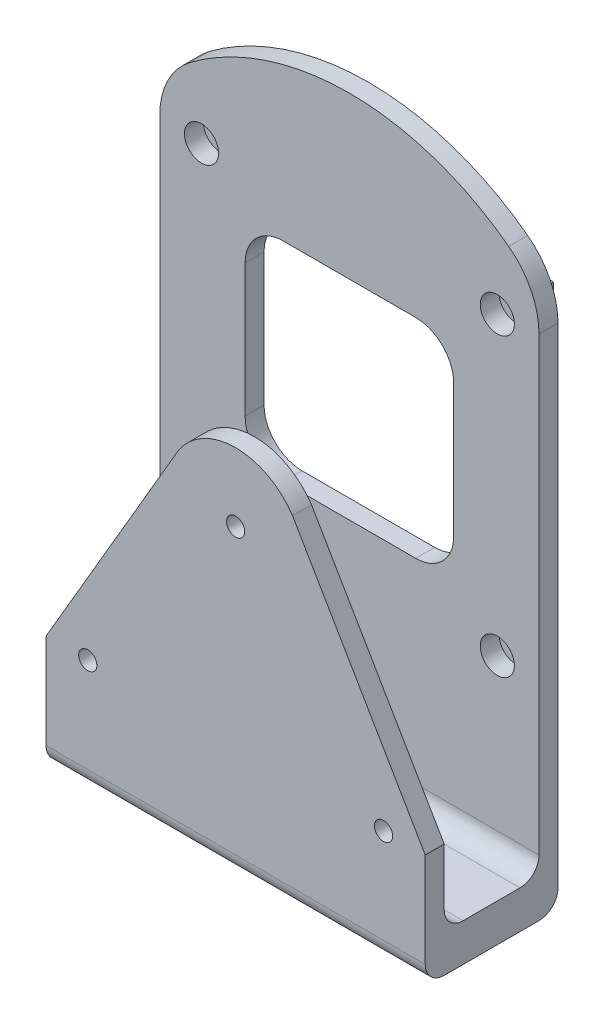
SolidWorks part; units mm, degrees
ref_plane "Спереди" through (0, 0, 0) normal (0, 0, 1) x (1, 0, 0)
ref_plane "Сверху" through (0, 0, 0) normal (0, 1, 0) x (1, 0, 0)
ref_plane "Справа" through (0, 0, 0) normal (1, 0, 0) x (0, 0, -1)
sketch "Эскиз1" plane through (0, 0, 0) normal (0, 0, 1) x (1, 0, 0)
  line L0 (50, 0) -> (-50, 0) construction
  line L1 (45, -46.9042) -> (45, 46.9042)
  line L2 (0, 0) -> (0, -65) construction
  line L3 (50, -48.9898) -> (50, 48.9898)
  line L4 (-50, -48.9898) -> (-50, 48.9898)
  line L5 (-45, -46.9042) -> (-45, 46.9042)
  line L6 (17.5, -27.5) -> (-17.5, -27.5)
  line L7 (27.5, -17.5) -> (27.5, 17.5)
  line L8 (17.5, 27.5) -> (-17.5, 27.5)
  line L9 (-27.5, -17.5) -> (-27.5, 17.5)
  line L10 (27.5, -27.5) -> (-27.5, 27.5) construction
  line L11 (27.5, 27.5) -> (-27.5, -27.5) construction
  line L12 (-33, -44.925) -> (-45, -44.925)
  line L13 (-33, -44.925) -> (-33, -33.075)
  line L14 (-33, -33.075) -> (-45, -33.075)
  line L15 (-45, -44.925) -> (-45, -33.075)
  line L16 (-0.1, 27.5) -> (0.1, 27.5)
  line L17 (-33, -44.925) -> (-45, -33.075) construction
  line L18 (-33, -33.075) -> (-45, -44.925) construction
  line L19 (33, -44.925) -> (45, -44.925)
  line L20 (33, -44.925) -> (33, -33.075)
  line L21 (33, -33.075) -> (45, -33.075)
  line L22 (-33, 33.075) -> (-45, 33.075)
  line L23 (-27.5, 0.1) -> (-27.5, -0.1)
  line L24 (-0.1, -27.5) -> (0.1, -27.5)
  line L25 (27.5, 0.1) -> (27.5, -0.1)
  line L26 (-33, 44.925) -> (-33, 33.075)
  line L27 (-33, 44.925) -> (-45, 44.925)
  line L28 (33, 44.925) -> (45, 44.925)
  line L29 (33, 44.925) -> (33, 33.075)
  line L30 (33, 33.075) -> (45, 33.075)
  arc A0 (-45, -46.9042) -> (45, -46.9042) centre (0, 0) ccw
  arc A1 (50, 48.9898) -> (-50, 48.9898) centre (0, 0) ccw
  arc A2 (45, 46.9042) -> (-45, 46.9042) centre (0, 0) ccw
  circle A3 centre (0, 0) radius 65 construction
  circle A4 centre (0, 0) radius 70 construction
  arc A5 (-50, -48.9898) -> (50, -48.9898) centre (0, 0) ccw
  circle A6 centre (-39, -39) radius 2.5
  circle A7 centre (39, -39) radius 4.5
  circle A8 centre (39, -39) radius 2.5
  circle A9 centre (-39, -39) radius 4.5
  circle A10 centre (39, 39) radius 2.5
  circle A11 centre (-39, 39) radius 4.5
  circle A12 centre (-39, 39) radius 2.5
  circle A13 centre (39, 39) radius 4.5
  arc A14 (17.5, -27.5) -> (27.5, -17.5) centre (17.5, -17.5) ccw
  arc A15 (-17.5, -27.5) -> (-27.5, -17.5) centre (-17.5, -17.5) cw
  arc A16 (-17.5, 27.5) -> (-27.5, 17.5) centre (-17.5, 17.5) ccw
  arc A17 (27.5, 17.5) -> (17.5, 27.5) centre (17.5, 17.5) ccw
  point P4 (66.9413, 20.466)
  point P14 (65, 0)
  dimension "D2" = 9
  dimension "D6" = 5
  dimension "D7" = 9
  dimension "D11" = 10
  dimension "D8" = 9
  dimension "D9" = 9
  dimension "D12" = 78
  dimension "D3" = 5
  dimension "D5" = 78
  dimension "D10" = 100
  dimension "D13" = 11.85
  dimension "D1" = 5
extrude "Extrude" add sketch "Эскиз1" along normal blind 5 contours L4 A5 L3 A1 A2 L1 A0 L5 | L1 A2 L5 A0 A8 A6 A10 A12 | L21 L20 L19 L1 A7 | L13 L14 L5 L12 A9 | L26 L27 L5 L22 A11 | L29 L30 L1 L28 A13 region at (0, -63.4189, 0) region at (39, -44.7564, 0) region at (-44.8314, -39, 0) region at (39, 33.2436, 0) region at (-44.8314, 39, 0) region at (0, -68.2795, 0)
fillet "Fillet1" radius 20 4 edges at (50, -48.9898, 2.5) (-50, -48.9898, 2.5) (-50, 48.9898, 2.5) (50, 48.9898, 2.5)
extrude "Boss-Extrude1" add sketch "Эскиз1<5>" against normal blind 3.85 contours L21 L20 L19 L1 A7 | L13 L14 L5 L12 A9 | L26 L27 L5 L22 A11 | L29 L30 L1 L28 A13 | A13 A10 | A11 A12 | A9 A6 | A7 A8 region at (39, -44.7564, 0) region at (-44.8314, -39, 0) region at (39, 33.2436, 0) region at (-44.8314, 39, 0) region at (34.6273, -39, 0) region at (-43.3727, -39, 0) region at (-43.3727, 39, 0) region at (34.6273, 39, 0)
sketch "Эскиз1<5>" plane through (0, 0, 0) normal (0, 0, 1) x (1, 0, 0) same geometry as "Эскиз1"
sketch "Sketch1" plane through (0, 0, 0) normal (0, 0, 1) x (1, 0, 0)
  line L0 (-50, -40) -> (-50, -84)
  line L1 (-50, -84) -> (50, -84)
  line L2 (50, -84) -> (50, -40)
  line L3 (-50, -84) -> (-50, -94)
  line L4 (-50, -94) -> (50, -94)
  line L5 (50, -94) -> (50, -84)
  circle A0 centre (-39, -39) radius 2.5 construction
  arc A1 (50, -40) -> (-50, -40) centre (0, 10) cw
  dimension "D1" = 45
  dimension "D2" = 10
extrude "Boss-Extrude3" add sketch "Sketch1" along normal blind 5 contours L2 A1 L0 L1 region at (0, -68.5287, 0)
extrude "Boss-Extrude4" add sketch "Sketch1<3>" along normal blind 30 contours L4 L5 L1 L3 region at (0, -89, 0)
sketch "Sketch1<3>" plane through (0, 0, 0) normal (0, 0, 1) x (1, 0, 0) same geometry as "Sketch1"
sketch "Sketch2" plane through (0, 0, 30) normal (0, 0, 1) x (1, 0, 0)
  line L1 (0, 0) -> (0, -84) construction
  line L2 (-50, -84) -> (50, -84) construction
  line L4 (-50, -84) -> (50, -84)
  line L5 (-50, -84) -> (-50, -64)
  line L6 (-50, -84) -> (-50, 40) construction
  line L7 (-50, -64) -> (-15, -4)
  line L8 (50, -84) -> (50, -64)
  line L9 (50, -64) -> (15, -4)
  line L10 (-39, -39) -> (-39, -64) construction
  line L11 (35, -61.6906) -> (39, -59.3812)
  line L12 (-39, -59.3812) -> (-43, -61.6906)
  line L13 (-43, -61.6906) -> (-43, -66.3094)
  line L14 (-43, -66.3094) -> (-39, -68.6188)
  line L15 (-39, -68.6188) -> (-35, -66.3094)
  line L16 (-35, -66.3094) -> (-35, -61.6906)
  line L17 (-35, -61.6906) -> (-39, -59.3812)
  line L18 (0, -9.3812) -> (-4, -11.6906)
  line L19 (-4, -11.6906) -> (-4, -16.3094)
  line L20 (-4, -16.3094) -> (0, -18.6188)
  line L21 (0, -18.6188) -> (4, -16.3094)
  line L22 (4, -16.3094) -> (4, -11.6906)
  line L23 (4, -11.6906) -> (0, -9.3812)
  line L24 (35, -66.3094) -> (35, -61.6906)
  line L25 (39, -68.6188) -> (35, -66.3094)
  line L26 (43, -66.3094) -> (39, -68.6188)
  line L27 (43, -61.6906) -> (43, -66.3094)
  line L28 (39, -59.3812) -> (43, -61.6906)
  arc A0 (-15, -4) -> (15, -4) centre (0, -14) cw
  circle A1 centre (0, -14) radius 2.4
  circle A2 centre (-39, -64) radius 2.4
  circle A3 centre (39, -64) radius 2.4
  circle A4 centre (-39, -64) radius 4 construction
  circle A5 centre (0, -14) radius 4 construction
  circle A6 centre (39, -64) radius 4 construction
  line M1 (-50, -94) -> (50, -94)
  line M2 (50, -94) -> (50, -84)
  line M3 (50, -84) -> (-50, -84)
  line M4 (-50, -84) -> (-50, -94)
  dimension "D4" = 4.8
  dimension "D6" = 4.8
  dimension "D7" = 20
  dimension "D1" = 15
  dimension "D2" = 70
  dimension "D3" = 10
  dimension "D5" = 20
  dimension "D8" = 8
  dimension "D9" = 8
extrude "Boss-Extrude5" add sketch "Sketch2" along normal blind 5 contours A0 L7 L5 L8 L9 L23 L22 L21 L20 L19 L18 L17 L16 L15 L14 L13 L12 L11 L28 L27 L26 L25 L24 M3 | M4 M1 M2 M3 | L28 L11 L24 L25 L26 L27 A3 | L22 L23 L18 L19 L20 L21 A1 | L16 L17 L12 L13 L14 L15 A2 region at (0, -49.7789, 30) region at (0, -89, 30) region at (37.0611, -60.6417, 30) region at (-37.0611, -60.6417, 30) region at (1.9389, -10.6417, 30)
fillet "Fillet2" radius 5 4 edges at (0, -94, 0) (0, -94, 35) (0, -84, 30) (0, -84, 5)
